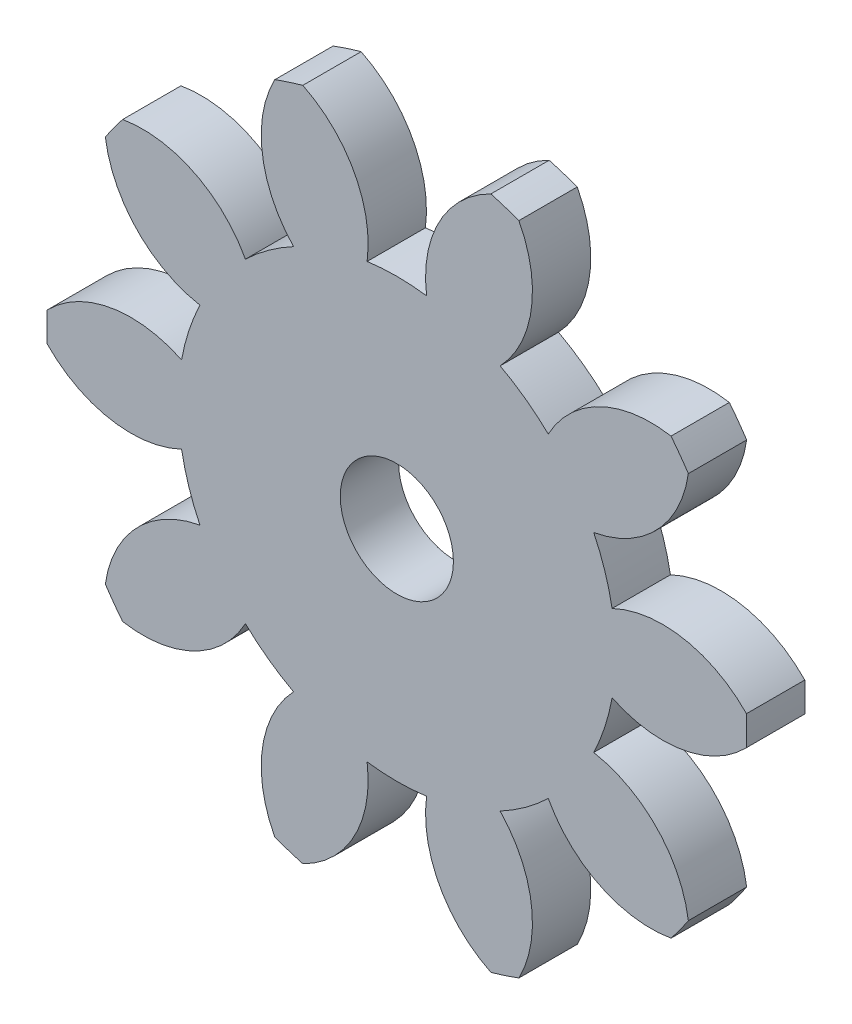
SolidWorks part; units mm, degrees
ref_plane "Front Plane" through (0, 0, 0) normal (0, 0, 1) x (1, 0, 0)
ref_plane "Top Plane" through (0, 0, 0) normal (0, 1, 0) x (1, 0, 0)
ref_plane "Right Plane" through (0, 0, 0) normal (1, 0, 0) x (0, 0, -1)
sketch "Sketch1" plane through (0, 0, 0) normal (0, 0, 1) x (1, 0, 0)
  circle A1 centre (0, 0) radius 18
  dimension "addendumDiameter" = 36
extrude "Boss-Extrude1" add sketch "Sketch1" along normal blind 3
sketch "Sketch2" plane through (0, 0, 3) normal (0, 0, 1) x (1, 0, 0)
  line L0 (0, 0) -> (0, 31) construction
  line L1 (0, 0) -> (-7.2275, 22.2439) construction
  line L2 (-2.2154, 14.8355) -> (-4.5716, 14.0699) construction
  circle A0 centre (0, 0) radius 14.0954 construction
  circle A1 centre (0, 0) radius 15 construction
  circle A2 centre (0, 0) radius 11.25 construction
  arc A5 (4.8367, 17.338) -> (1.5299, 11.1455) centre (7.4758, 11.9496) ccw
  arc A8 (4.8367, 17.338) -> (-4.8367, 17.338) centre (0, 0) ccw
  circle A9 centre (0, 0) radius 18 construction
  arc A10 (1.5299, 11.1455) -> (-1.5299, 11.1455) centre (0, 0) ccw
  circle A11 centre (0, 0) radius 18 construction
  arc A12 (-4.8367, 17.338) -> (-1.5299, 11.1455) centre (-7.4758, 11.9496) cw
  dimension "Dedendum Circle" = 22.5
  dimension "Base Diameter" = 28.1908
  dimension "D7" = 30
  dimension "D4" = 6
  dimension "D1" = 6
  dimension "D3" = 18
  dimension "D2" = 2.3562
extrude "Cut-Extrude1" cut sketch "Sketch2" against normal blind 3
pattern_circular "CirPattern1" count 10 over 360 about axis through (0, 0, 3) along (0, 0, 1) of "Cut-Extrude1"
ref_axis "Axis1" through (0, 0, 0) along (0, 0, 1)
sketch "Sketch4" plane through (0, 0, 3) normal (0, 0, 1) x (1, 0, 0)
  line L1 (-0.241, 2.9) -> (0.241, 2.9)
  arc A1 (-0.241, 2.9) -> (0.241, 2.9) centre (0, 0) ccw
  dimension "D2" = 5.82
  dimension "D1" = 2.9
extrude "Cut-Extrude3" cut sketch "Sketch4" against normal through all
equation "\"module\"= 3"
equation "\"teeth\"= 10"
equation "\"pressureAngle\"= 20deg"
equation "\"gearThickness\"= 3"
equation "\"addendumFactor\"= 1"
equation "\"dedendumFactor\"= 1.25"
equation "\"pitch\"= 1 / \"module\""
equation "\"pitchDiameter\"= \"teeth\" / \"pitch\""
equation "\"addendum\"= \"addendumFactor\" / \"pitch\""
equation "\"dedendum\"= \"dedendumFactor\" / \"pitch\""
equation "\"D1@Boss-Extrude1\"=\"gearThickness\""
equation "\"D3@Sketch2\"=180/\"teeth\""
equation "\"addendumDiameter@Sketch1\"=\"pitchDiameter\" + 2 * \"addendum\""
equation "\"Dedendum Circle@Sketch2\" = \"pitchDiameter\" - 2 * \"dedendum\""
equation "\"Base Diameter@Sketch2\" = \"pitchDiameter\" * cos ( \"pressureAngle\" ) "
equation "\"D7@Sketch2\"= \"pitchDiameter\""
equation "\"D4@Sketch2\"= \"pitchDiameter\" / 5"
equation "\"D1@Sketch2\"= \"pitchDiameter\" / 5"
equation "\"D2@Sketch2\"= PI / 2 / \"pitch\" / 2"
equation "\"D1@CirPattern1\"= \"teeth\""
